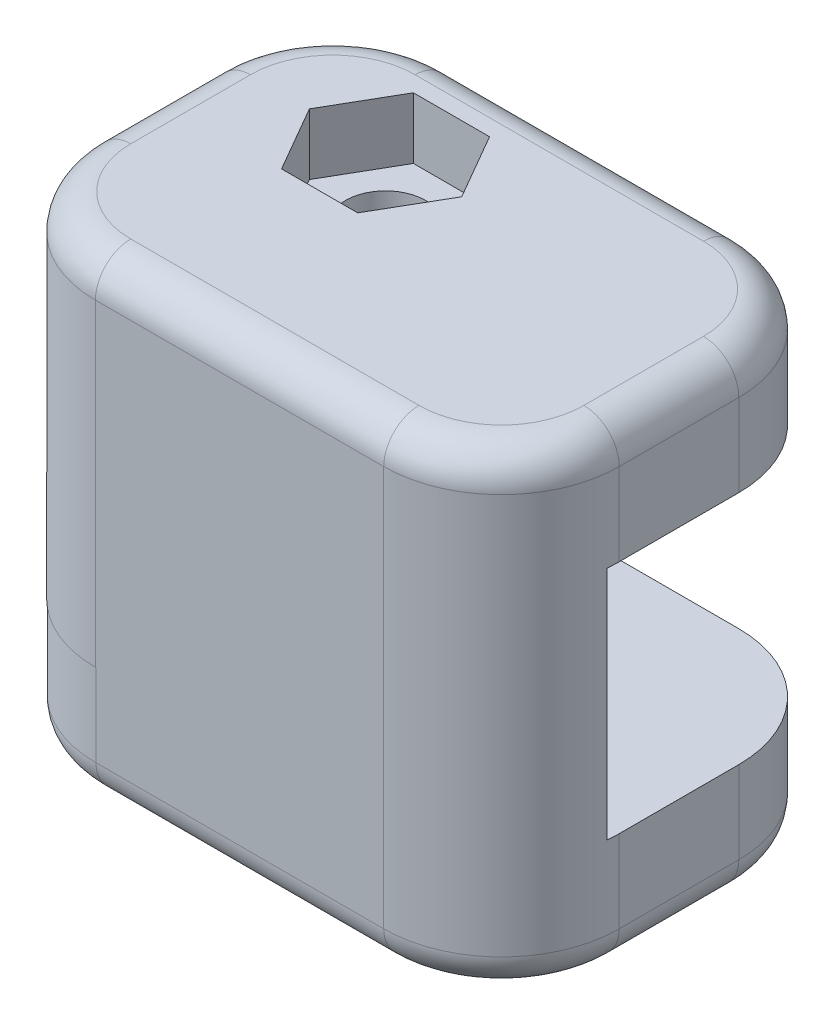
SolidWorks part; units mm, degrees
ref_plane "Front Plane" through (0, 0, 0) normal (0, 0, 1) x (1, 0, 0)
ref_plane "Top Plane" through (0, 0, 0) normal (0, 1, 0) x (1, 0, 0)
ref_plane "Right Plane" through (0, 0, 0) normal (1, 0, 0) x (0, 0, -1)
sketch "Sketch1" plane through (0, 0, 0) normal (0, 1, 0) x (1, 0, 0)
  line L0 (0, 0) -> (10, 0) construction
  line L1 (0, 5) -> (10, 5)
  line L4 (15, 0) -> (15, -5.0781)
  line L5 (-2.2415, -10.0781) -> (10, -10.0781)
  line L6 (0, 5) -> (-2.2415, 5)
  line L7 (-7.2415, 0) -> (-7.2415, -5.0781)
  arc A1 (15, 0) -> (10, 5) centre (10, 0) ccw
  arc A3 (15, -5.0781) -> (10, -10.0781) centre (10, -5.0781) cw
  arc A4 (-2.2415, -10.0781) -> (-7.2415, -5.0781) centre (-2.2415, -5.0781) cw
  arc A5 (-2.2415, 5) -> (-7.2415, 0) centre (-2.2415, 0) ccw
  circle A7 centre (0, 0) radius 1.7
  point P3 (5, 0)
  dimension "D1" = 10
  dimension "D2" = 5
  dimension "D3" = 5
  dimension "D4" = 5
  dimension "D5" = 5
  dimension "D6" = 3.4
extrude "Boss-Extrude1" add sketch "Sketch1" along normal blind 5
sketch "Sketch2" plane through (0, 5, 0) normal (0, 1, 0) x (1, 0, 0)
  line L0 (0, 0) -> (10, 0) construction
  line L3 (-5.5781, 0) -> (-7.2415, 0)
  line L4 (-7.2415, 0) -> (-7.2415, -5.0781)
  line L5 (-2.2415, -10.0781) -> (10, -10.0781)
  line L8 (-2.2415, -10.0781) -> (10, -10.0781) construction
  line L9 (0, 0) -> (10, 0) construction
  line L11 (0, -5.5781) -> (14.9749, -5.5781)
  arc A4 (-7.2415, -5.0781) -> (-2.2415, -10.0781) centre (-2.2415, -5.0781) ccw
  arc A5 (-5.5781, 0) -> (0, -5.5781) centre (0, 0) ccw
  arc A9 (10, -10.0781) -> (15, -5.0781) centre (10, -5.0781) ccw construction
  arc A10 (10, -10.0781) -> (14.9749, -5.5781) centre (10, -5.0781) ccw
  point P3 (5, 0)
  point P4 (5, 0)
  dimension "D1" = 4.5
extrude "Boss-Extrude2" add sketch "Sketch2" against normal blind 15
sketch "Sketch3" plane through (0, -10, 0) normal (0, -1, 0) x (-1, 0, 0)
  line L1 (-14.9749, -5.5781) -> (7.2415, -5.5781)
  line L2 (-14.9749, -5.5781) -> (-14.9749, 0)
  line L3 (-14.9749, 0) -> (7.2415, 0)
  line L4 (7.2415, -5.5781) -> (7.2415, 0)
extrude "Cut-Extrude1" cut sketch "Sketch3" against normal blind 7
sketch "Sketch4" plane through (0, -10, 0) normal (0, -1, 0) x (1, 0, 0)
  line L0 (-7.2164, 5.5781) -> (-7.2164, 10.0781) construction
  line L1 (-7.2164, 10.0781) -> (-2.2415, 10.0781) construction
  line L2 (15, 0) -> (15, -5) construction
  line L3 (15, -5) -> (10, -5) construction
  line L5 (10, -5) -> (-2.2164, -5)
  line L6 (15, 0) -> (15, 5.0781)
  line L7 (10, 10.0781) -> (-2.2164, 10.0781)
  line L8 (-7.2164, 0) -> (-7.2164, 5.0781)
  circle A0 centre (0, 0) radius 1.7
  circle A1 centre (0, 0) radius 1.7 construction
  arc A2 (-2.2164, -5) -> (-7.2164, 0) centre (-2.2164, 0) cw
  arc A3 (-2.2164, 10.0781) -> (-7.2164, 5.0781) centre (-2.2164, 5.0781) ccw
  arc A4 (15, 5.0781) -> (10, 10.0781) centre (10, 5.0781) ccw
  arc A5 (10, -5) -> (15, 0) centre (10, 0) ccw
  dimension "D1" = 5
extrude "Boss-Extrude3" add sketch "Sketch4" along normal blind 5
sketch "Sketch5" plane through (0, 5, 0) normal (0, 1, 0) x (1, 0, 0)
  line L1 (3.2332, 0) -> (1.6166, 2.8)
  line L2 (1.6166, 2.8) -> (-1.6166, 2.8)
  line L3 (-1.6166, 2.8) -> (-3.2332, 0)
  line L4 (-3.2332, 0) -> (-1.6166, -2.8)
  line L5 (-1.6166, -2.8) -> (1.6166, -2.8)
  line L6 (1.6166, -2.8) -> (3.2332, 0)
  circle A0 centre (0, 0) radius 2.8 construction
  dimension "D1" = 5.6
  dimension "D2" = 2.8
extrude "Cut-Extrude2" cut sketch "Sketch5" against normal blind 2.6
fillet "Fillet1" radius 1.5 16 edges at (3.8918, -15, -5) (-5.752, -15, -3.5355) (-7.2164, -15, 2.5391) (-5.752, -15, 8.6137) (3.8918, -15, 10.0781) (13.5355, -15, 8.6137) (15, -15, 2.5391) (15, 5, 2.5391) (13.5355, 5, 8.6137) (3.8793, 5, 10.0781) (-5.777, 5, 8.6137) (-7.2415, 5, 2.5391) (-5.777, 5, -3.5355) (3.8793, 5, -5) (13.5355, -15, -3.5355) (13.5355, 5, -3.5355)
